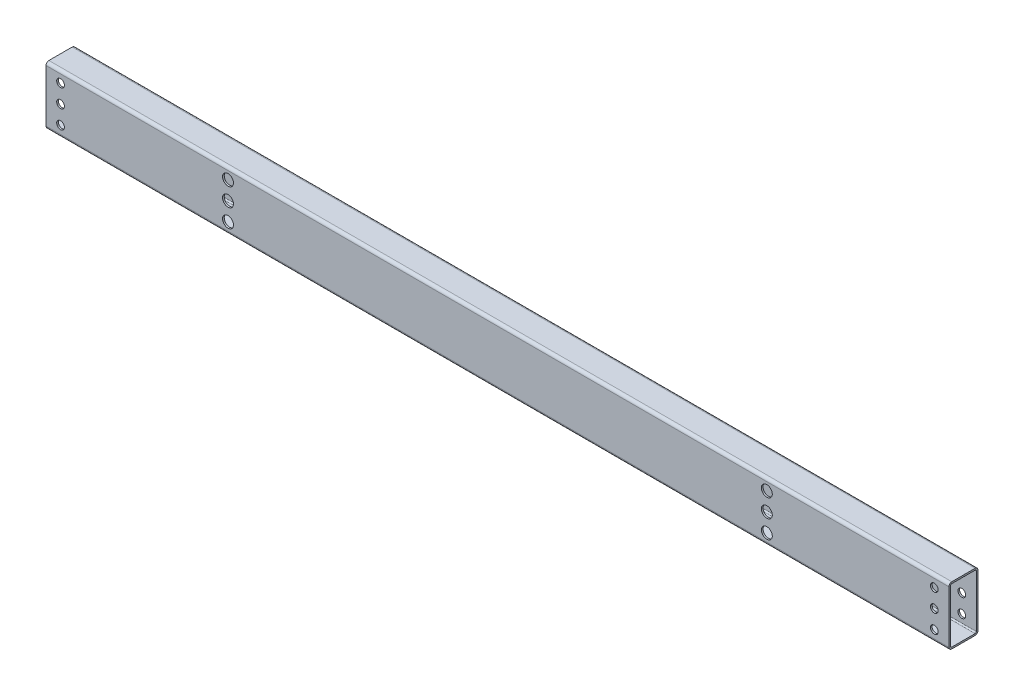
SolidWorks part; units mm, degrees
material "6061-T6 (SS)"
ref_plane "Front" through (0, 0, 0) normal (0, 0, 1) x (1, 0, 0)
ref_plane "Top" through (0, 0, 0) normal (0, 1, 0) x (1, 0, 0)
ref_plane "Right" through (0, 0, 0) normal (1, 0, 0) x (0, 0, -1)
sketch "Sketch1" plane through (0, 0, 0) normal (1, 0, 0) x (0, 0, -1)
  line L0 (10.16, -25.4) -> (-10.16, -25.4)
  line L1 (12.7, -22.86) -> (12.7, 22.86)
  line L2 (10.16, 25.4) -> (-10.16, 25.4)
  line L3 (-12.7, -22.86) -> (-12.7, 22.86)
  line L4 (12.7, -25.4) -> (-12.7, 25.4) construction
  line L5 (12.7, 25.4) -> (-12.7, -25.4) construction
  arc A0 (-10.16, -25.4) -> (-12.7, -22.86) centre (-10.16, -22.86) cw
  arc A1 (10.16, -25.4) -> (12.7, -22.86) centre (10.16, -22.86) ccw
  arc A2 (12.7, 22.86) -> (10.16, 25.4) centre (10.16, 22.86) ccw
  arc A3 (-10.16, 25.4) -> (-12.7, 22.86) centre (-10.16, 22.86) ccw
  point P0 (0, 0)
  dimension "D3" = 2.54
  dimension "D1" = 25.4
  dimension "D2" = 50.8
extrude "Extrude-Thin1" add sketch "Sketch1" along normal mid plane 787.4 thin thin type one direction reverse wall 1.4478
hole_wizard "1/4 Clearance Hole1" positions "Sketch2" profile "Sketch3" hole size "1/4" standard "ANSI Inch" end condition through all
sketch "Sketch2" plane through (0, 0, -12.7) normal (0, 0, -1) x (-1, 0, 0)
  line L0 (-393.7, -22.86) -> (-393.7, 22.86) construction
  line L1 (-393.7, 25.4) -> (393.7, 25.4) construction
  line L2 (-393.7, -25.4) -> (393.7, -25.4) construction
  line L3 (-381, 15.875) -> (-381, -15.875) construction
  line L4 (0, 0) -> (0, -37.3791) construction
  point P0 (-381, 15.875)
  point P2 (-381, -15.875)
  point P15 (-381, 0)
  point P23 (381, -15.875)
  point P24 (381, 0)
  point P25 (381, 15.875)
  dimension "D1" = 12.7
  dimension "D2" = 9.525
  dimension "D3" = 9.525
sketch "Sketch3" plane through (381, 15.875, -12.7) normal (1, 0, 0) x (0, 1, 0)
  line L0 (0, 0) -> (0, 25.4)
  line L1 (0, 25.4) -> (3.3782, 25.4)
  line L2 (3.3782, 25.4) -> (3.3782, 0)
  line L5 (3.3782, 0) -> (0, 0)
  line L11 (0, -6.35) -> (0, 107.95) construction
  dimension "Thru Hole Dia." = 6.7564
  dimension "Thru Hole Depth" = 25.4
hole_wizard "3/8 (0.375) Diameter Hole1" positions "Sketch4" profile "Sketch5" hole size "3/8" standard "ANSI Inch" end condition through all
sketch "Sketch4" plane through (0, 0, -12.7) normal (0, 0, -1) x (-1, 0, 0)
  line L0 (-234.95, 15.875) -> (-234.95, -15.875) construction
  line L2 (-393.7, 25.4) -> (393.7, 25.4) construction
  line L3 (-393.7, -25.4) -> (393.7, -25.4) construction
  line L4 (0, 0) -> (0, -51.4899) construction
  point P19 (-234.95, 15.875)
  point P21 (-234.95, 0)
  point P23 (-234.95, -15.875)
  point P42 (234.95, -15.875)
  point P43 (234.95, 0)
  point P44 (234.95, 15.875)
  dimension "D1" = 9.525
  dimension "D2" = 9.525
  dimension "D3" = 469.9
sketch "Sketch5" plane through (234.95, 15.875, -12.7) normal (1, 0, 0) x (0, 1, 0)
  line L0 (0, 0) -> (0, 25.4)
  line L1 (0, 25.4) -> (4.7625, 25.4)
  line L2 (4.7625, 25.4) -> (4.7625, 0)
  line L5 (4.7625, 0) -> (0, 0)
  line L11 (0, -6.35) -> (0, 107.95) construction
  dimension "Thru Hole Dia." = 9.525
  dimension "Thru Hole Depth" = 25.4
sketch "Sketch6" plane through (0, 0, -12.7) normal (0, 0, -1) x (-1, 0, 0)
  line L0 (-393.7, -25.4) -> (393.7, -25.4) construction
  line L2 (-120.65, -25.4) -> (-107.95, -25.4)
  line L3 (-120.65, -25.4) -> (-120.65, 15.875)
  line L4 (-117.475, 19.05) -> (-111.125, 19.05)
  line L5 (-107.95, -25.4) -> (-107.95, 15.875)
  line L6 (-44.45, -25.4) -> (-31.75, -25.4)
  line L11 (-44.45, -25.4) -> (-44.45, 15.875)
  line L12 (-41.275, 19.05) -> (-34.925, 19.05)
  line L13 (-31.75, -25.4) -> (-31.75, 15.875)
  line L14 (31.75, -25.4) -> (44.45, -25.4)
  line L15 (31.75, -25.4) -> (31.75, 15.875)
  line L16 (34.925, 19.05) -> (41.275, 19.05)
  line L17 (44.45, -25.4) -> (44.45, 15.875)
  line L18 (107.95, -25.4) -> (120.65, -25.4)
  line L19 (107.95, -25.4) -> (107.95, 15.875)
  line L20 (111.125, 19.05) -> (117.475, 19.05)
  line L21 (120.65, -25.4) -> (120.65, 15.875)
  line L22 (0, 0) -> (0, -9.525) construction
  arc A0 (-111.125, 19.05) -> (-107.95, 15.875) centre (-111.125, 15.875) cw
  arc A1 (-120.65, 15.875) -> (-117.475, 19.05) centre (-117.475, 15.875) cw
  arc A4 (-34.925, 19.05) -> (-31.75, 15.875) centre (-34.925, 15.875) cw
  arc A5 (-44.45, 15.875) -> (-41.275, 19.05) centre (-41.275, 15.875) cw
  arc A6 (41.275, 19.05) -> (44.45, 15.875) centre (41.275, 15.875) cw
  arc A7 (31.75, 15.875) -> (34.925, 19.05) centre (34.925, 15.875) cw
  arc A8 (117.475, 19.05) -> (120.65, 15.875) centre (117.475, 15.875) cw
  arc A9 (107.95, 15.875) -> (111.125, 19.05) centre (111.125, 15.875) cw
  dimension "D1" = 3.175
  dimension "D2" = 12.7
  dimension "D3" = 44.45
  dimension "D5" = 76.2
  dimension "D4" = 4
extrude "Cut-Extrude1" cut sketch "Sketch6" against normal blind 9.525
